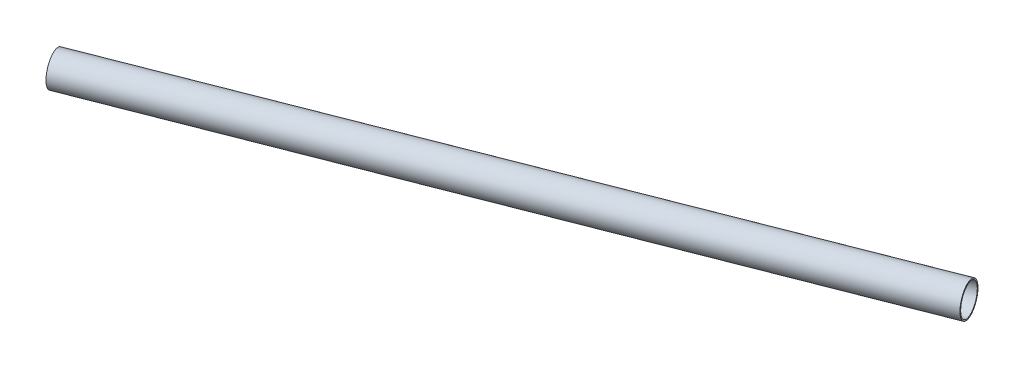
SolidWorks part; units mm, degrees
ref_plane "Front Plane" through (0, 0, 0) normal (0, 0, 1) x (1, 0, 0)
ref_plane "Top Plane" through (0, 0, 0) normal (0, 1, 0) x (1, 0, 0)
ref_plane "Right Plane" through (0, 0, 0) normal (1, 0, 0) x (0, 0, -1)
sketch "Sketch1" plane through (0, 0, 0) normal (0, 1, 0) x (1, 0, 0)
  line L0 (0, 0) -> (640, 0) construction
  line L1 (0, 0) -> (591.2829, 244.9174)
  line L2 (0, 0) -> (591.2829, -244.9174)
  line L3 (0, 0) -> (244.9174, -591.2829)
  line L4 (0, 0) -> (-244.9174, -591.2829)
  line L5 (0, 0) -> (-591.2829, -244.9174)
  line L6 (0, 0) -> (-591.2829, 244.9174)
  line L7 (0, 0) -> (-244.9174, 591.2829)
  line L8 (0, 0) -> (244.9174, 591.2829)
  line L9 (0, 145) -> (55, 145) construction
  line L10 (0, 0) -> (100, 0) construction
  line L11 (0, 0) -> (0, 145) construction
  line L14 (100, 0) -> (100, 145) construction
  circle A0 centre (0, 0) radius 640 construction
  point P15 (0, 0)
  dimension "D1" = 1280
  dimension "D2" = 22.5
  dimension "D4" = 145
  dimension "D5" = 100
  dimension "D6" = 55
  dimension "D3" = 8
sketch "Sketch2" plane through (0, 0, 0) normal (0, 1, 0) x (1, 0, 0)
  line L0 (-486.9956, 169.5033) -> (-66.9956, 169.5033) construction
  line L1 (-188.7141, -86.1278) -> (-188.7141, 241.8722) construction
  line L2 (525.6625, -1048.8053) -> (466.9027, -726.1115) construction
sketch "Sketch3" plane through (0, 0, 0) normal (0, 1, 0) x (1, 0, 0)
  line L0 (0, 0) -> (381.2468, 0) construction
  line L5 (0, 0) -> (0, 199.4415) construction
  line L6 (-10.2736, 158.9263) -> (10.2736, 158.9263)
  line L7 (10.2736, 158.9263) -> (13.1995, 163.9003)
  line L8 (13.1995, 163.9003) -> (45.5131, 148.2994)
  line L9 (45.5131, 148.2994) -> (66.2904, 80.9335)
  line L10 (66.2904, 80.9335) -> (73.8622, 80.9335)
  line L11 (73.8622, 80.9335) -> (86.8684, 42.4396)
  line L12 (86.8684, 42.4396) -> (86.8684, 30.0712)
  line L13 (86.8684, 30.0712) -> (81.3965, 24.5993)
  line L14 (81.3965, 24.5993) -> (81.3965, -24.5993)
  line L15 (-5.8349, 67.4929) -> (5.8349, 67.4929) construction
  line L16 (16.6008, 64.1674) -> (16.6008, 27.6557) construction
  line L17 (16.6008, 27.6557) -> (13.2646, 22.809) construction
  line L18 (13.2646, 22.809) -> (13.2646, -22.809) construction
  line L19 (5.8349, 128.0146) -> (5.8349, 107.4452)
  line L22 (5.8349, 107.4452) -> (9.2702, 107.4452)
  line L25 (9.2702, 107.4452) -> (10.663, 103.7163)
  line L26 (10.663, 103.7163) -> (20.7578, 101.0699)
  line L27 (20.7578, 101.0699) -> (32.199, 111.7601)
  line L28 (32.199, 111.7601) -> (32.199, 123.5038)
  line L29 (32.199, 123.5038) -> (24.9078, 123.5038)
  line L30 (24.9078, 123.5038) -> (13.8412, 132.5856)
  line L31 (13.8412, 132.5856) -> (9.2702, 132.5856)
  line L32 (9.2702, 132.5856) -> (5.8349, 128.0146)
  line L33 (41.9414, 39.7891) -> (51.4866, 54.1602)
  line L34 (51.4866, 54.1602) -> (55.4027, 54.1602)
  line L35 (55.4027, 54.1602) -> (58.1637, 51.3993)
  line L36 (58.1637, 51.3993) -> (58.1637, 43.1872)
  line L37 (58.1637, 43.1872) -> (66.3555, 28.462)
  line L38 (66.3555, 28.462) -> (66.3555, 24.0728)
  line L39 (66.3555, 24.0728) -> (62.2596, 17.9061)
  line L40 (62.2596, 17.9061) -> (47.8497, 18.1669)
  line L41 (47.8497, 18.1669) -> (41.9414, 27.1878)
  line L42 (41.9414, 27.1878) -> (41.9414, 39.7891)
  line L43 (-41.9414, 27.1878) -> (-41.9414, 39.7891)
  line L44 (-47.8497, 18.1669) -> (-41.9414, 27.1878)
  line L45 (-62.2596, 17.9061) -> (-47.8497, 18.1669)
  line L46 (-66.3555, 24.0728) -> (-62.2596, 17.9061)
  line L47 (-66.3555, 28.462) -> (-66.3555, 24.0728)
  line L48 (-58.1637, 43.1872) -> (-66.3555, 28.462)
  line L49 (-58.1637, 51.3993) -> (-58.1637, 43.1872)
  line L50 (-55.4027, 54.1602) -> (-58.1637, 51.3993)
  line L51 (-51.4866, 54.1602) -> (-55.4027, 54.1602)
  line L52 (-41.9414, 39.7891) -> (-51.4866, 54.1602)
  line L53 (-9.2702, 132.5856) -> (-5.8349, 128.0146)
  line L54 (-13.8412, 132.5856) -> (-9.2702, 132.5856)
  line L55 (-24.9078, 123.5038) -> (-13.8412, 132.5856)
  line L56 (-32.199, 123.5038) -> (-24.9078, 123.5038)
  line L57 (-32.199, 111.7601) -> (-32.199, 123.5038)
  line L58 (-20.7578, 101.0699) -> (-32.199, 111.7601)
  line L59 (-10.663, 103.7163) -> (-20.7578, 101.0699)
  line L60 (-9.2702, 107.4452) -> (-10.663, 103.7163)
  line L61 (-5.8349, 107.4452) -> (-9.2702, 107.4452)
  line L62 (-5.8349, 128.0146) -> (-5.8349, 107.4452)
  line L63 (-13.2646, 22.809) -> (-13.2646, -22.809) construction
  line L64 (-16.6008, 27.6557) -> (-13.2646, 22.809) construction
  line L65 (-16.6008, 64.1674) -> (-16.6008, 27.6557) construction
  line L66 (-81.3965, 24.5993) -> (-81.3965, -24.5993)
  line L67 (-86.8684, 30.0712) -> (-81.3965, 24.5993)
  line L68 (-86.8684, 42.4396) -> (-86.8684, 30.0712)
  line L69 (-73.8622, 80.9335) -> (-86.8684, 42.4396)
  line L70 (-66.2904, 80.9335) -> (-73.8622, 80.9335)
  line L71 (-45.5131, 148.2994) -> (-66.2904, 80.9335)
  line L72 (-13.1995, 163.9003) -> (-45.5131, 148.2994)
  line L73 (-10.2736, 158.9263) -> (-13.1995, 163.9003)
  line L74 (-10.2736, -158.9263) -> (-13.1995, -163.9003)
  line L75 (-13.1995, -163.9003) -> (-45.5131, -148.2994)
  line L76 (-45.5131, -148.2994) -> (-66.2904, -80.9335)
  line L77 (-66.2904, -80.9335) -> (-73.8622, -80.9335)
  line L78 (-73.8622, -80.9335) -> (-86.8684, -42.4396)
  line L79 (-86.8684, -42.4396) -> (-86.8684, -30.0712)
  line L80 (-86.8684, -30.0712) -> (-81.3965, -24.5993)
  line L81 (-16.6008, -64.1674) -> (-16.6008, -27.6557) construction
  line L82 (-16.6008, -27.6557) -> (-13.2646, -22.809) construction
  line L83 (-5.8349, -128.0146) -> (-5.8349, -107.4452)
  line L84 (-5.8349, -107.4452) -> (-9.2702, -107.4452)
  line L85 (-9.2702, -107.4452) -> (-10.663, -103.7163)
  line L86 (-10.663, -103.7163) -> (-20.7578, -101.0699)
  line L87 (-20.7578, -101.0699) -> (-32.199, -111.7601)
  line L88 (-32.199, -111.7601) -> (-32.199, -123.5038)
  line L89 (-32.199, -123.5038) -> (-24.9078, -123.5038)
  line L90 (-24.9078, -123.5038) -> (-13.8412, -132.5856)
  line L91 (-13.8412, -132.5856) -> (-9.2702, -132.5856)
  line L92 (-9.2702, -132.5856) -> (-5.8349, -128.0146)
  line L93 (-41.9414, -39.7891) -> (-51.4866, -54.1602)
  line L94 (-51.4866, -54.1602) -> (-55.4027, -54.1602)
  line L95 (-55.4027, -54.1602) -> (-58.1637, -51.3993)
  line L96 (-58.1637, -51.3993) -> (-58.1637, -43.1872)
  line L97 (-58.1637, -43.1872) -> (-66.3555, -28.462)
  line L98 (-66.3555, -28.462) -> (-66.3555, -24.0728)
  line L99 (-66.3555, -24.0728) -> (-62.2596, -17.9061)
  line L100 (-62.2596, -17.9061) -> (-47.8497, -18.1669)
  line L101 (-47.8497, -18.1669) -> (-41.9414, -27.1878)
  line L102 (-41.9414, -27.1878) -> (-41.9414, -39.7891)
  line L103 (41.9414, -27.1878) -> (41.9414, -39.7891)
  line L104 (47.8497, -18.1669) -> (41.9414, -27.1878)
  line L105 (62.2596, -17.9061) -> (47.8497, -18.1669)
  line L106 (66.3555, -24.0728) -> (62.2596, -17.9061)
  line L107 (66.3555, -28.462) -> (66.3555, -24.0728)
  line L108 (58.1637, -43.1872) -> (66.3555, -28.462)
  line L109 (58.1637, -51.3993) -> (58.1637, -43.1872)
  line L110 (55.4027, -54.1602) -> (58.1637, -51.3993)
  line L111 (51.4866, -54.1602) -> (55.4027, -54.1602)
  line L112 (41.9414, -39.7891) -> (51.4866, -54.1602)
  line L113 (9.2702, -132.5856) -> (5.8349, -128.0146)
  line L114 (13.8412, -132.5856) -> (9.2702, -132.5856)
  line L115 (24.9078, -123.5038) -> (13.8412, -132.5856)
  line L116 (32.199, -123.5038) -> (24.9078, -123.5038)
  line L117 (32.199, -111.7601) -> (32.199, -123.5038)
  line L118 (20.7578, -101.0699) -> (32.199, -111.7601)
  line L119 (10.663, -103.7163) -> (20.7578, -101.0699)
  line L120 (9.2702, -107.4452) -> (10.663, -103.7163)
  line L121 (5.8349, -107.4452) -> (9.2702, -107.4452)
  line L122 (5.8349, -128.0146) -> (5.8349, -107.4452)
  line L123 (16.6008, -27.6557) -> (13.2646, -22.809) construction
  line L124 (16.6008, -64.1674) -> (16.6008, -27.6557) construction
  line L125 (-5.8349, -67.4929) -> (5.8349, -67.4929) construction
  line L126 (86.8684, -30.0712) -> (81.3965, -24.5993)
  line L127 (86.8684, -42.4396) -> (86.8684, -30.0712)
  line L128 (73.8622, -80.9335) -> (86.8684, -42.4396)
  line L129 (66.2904, -80.9335) -> (73.8622, -80.9335)
  line L130 (45.5131, -148.2994) -> (66.2904, -80.9335)
  line L131 (13.1995, -163.9003) -> (45.5131, -148.2994)
  line L132 (10.2736, -158.9263) -> (13.1995, -163.9003)
  line L133 (-10.2736, -158.9263) -> (10.2736, -158.9263)
  line L134 (-5.3457, 68.4929) -> (5.3457, 68.4929)
  line L135 (17.6008, 64.1674) -> (17.6008, 27.3448)
  line L136 (17.6008, 27.3448) -> (14.2646, 22.498)
  line L137 (14.2646, 22.498) -> (14.2646, -22.498)
  line L138 (-17.6008, 64.1674) -> (-17.6008, 27.3448)
  line L139 (-17.6008, 27.3448) -> (-14.2646, 22.498)
  line L140 (-5.3457, 68.4929) -> (5.3457, 68.4929) construction
  line L141 (14.2646, 22.498) -> (14.2646, -22.498) construction
  line L142 (17.6008, -27.3448) -> (14.2646, -22.498) construction
  line L143 (17.6008, -64.1674) -> (17.6008, -27.3448) construction
  line L144 (-14.2646, 22.498) -> (-14.2646, -22.498)
  line L145 (17.6008, -64.1674) -> (17.6008, -27.3448)
  line L146 (17.6008, -27.3448) -> (14.2646, -22.498)
  line L147 (-17.6008, -27.3448) -> (-14.2646, -22.498)
  line L148 (-17.6008, -64.1674) -> (-17.6008, -27.3448)
  line L149 (-5.3457, -68.4929) -> (5.3457, -68.4929)
  arc A0 (5.8349, 67.4929) -> (16.6008, 64.0252) centre (10.663, 64.0364) cw construction
  arc A5 (-5.8349, 67.4929) -> (-16.6008, 64.0252) centre (-10.663, 64.0364) ccw construction
  arc A6 (-5.8349, -67.4929) -> (-16.6008, -64.0252) centre (-10.663, -64.0364) cw construction
  arc A7 (5.8349, -67.4929) -> (16.6008, -64.0252) centre (10.663, -64.0364) ccw construction
  arc A8 (-5.3457, 68.4929) -> (-17.6008, 64.0234) centre (-10.663, 64.0364) ccw
  arc A9 (5.3457, 68.4929) -> (17.6008, 64.0234) centre (10.663, 64.0364) cw
  arc A10 (-5.3457, 68.4929) -> (-17.6008, 64.0234) centre (-10.663, 64.0364) ccw construction
  arc A11 (5.3457, -68.4929) -> (17.6008, -64.0234) centre (10.663, -64.0364) ccw
  arc A12 (-5.3457, -68.4929) -> (-17.6008, -64.0234) centre (-10.663, -64.0364) cw
  ellipse E0 centre (11.3851, 149.6854) end of major axis (12.0553, 155.2702) minor radius 3.0047
  ellipse E1 centre (33.6925, 82.363) end of major axis (41.1096, 88.3895) minor radius 4.3287
  ellipse E2 centre (44.8955, 74.0187) end of major axis (51.4866, 79.374) minor radius 4.6847
  ellipse E3 centre (66.3555, 66.447) end of major axis (67.1471, 72.2416) minor radius 3.5711
  ellipse E4 centre (-66.3555, 66.447) end of major axis (-67.1471, 72.2416) minor radius 3.5711
  ellipse E5 centre (-44.8955, 74.0187) end of major axis (-51.4866, 79.374) minor radius 4.6847
  ellipse E6 centre (-33.6925, 82.363) end of major axis (-41.1096, 88.3895) minor radius 4.3287
  ellipse E7 centre (-11.3851, 149.6854) end of major axis (-12.0553, 155.2702) minor radius 3.0047
  ellipse E8 centre (-11.3851, -149.6854) end of major axis (-12.0553, -155.2702) minor radius 3.0047
  ellipse E9 centre (-33.6925, -82.363) end of major axis (-41.1096, -88.3895) minor radius 4.3287
  ellipse E10 centre (-44.8955, -74.0187) end of major axis (-51.4866, -79.374) minor radius 4.6847
  ellipse E11 centre (-66.3555, -66.447) end of major axis (-67.1471, -72.2416) minor radius 3.5711
  ellipse E12 centre (66.3555, -66.447) end of major axis (67.1471, -72.2416) minor radius 3.5711
  ellipse E13 centre (44.8955, -74.0187) end of major axis (51.4866, -79.374) minor radius 4.6847
  ellipse E14 centre (33.6925, -82.363) end of major axis (41.1096, -88.3895) minor radius 4.3287
  ellipse E15 centre (11.3851, -149.6854) end of major axis (12.0553, -155.2702) minor radius 3.0047
  point P117 (0, 67.4929)
  point P126 (0, 158.9263)
  point P180 (0, -158.9263)
  point P181 (0, -67.4929)
  point P190 (-81.3965, 0)
  point P193 (-13.2646, 0)
  point P234 (13.2646, 0)
  point P237 (81.3965, 0)
  point P261 (0, 68.4929)
  point P271 (14.2646, 0)
  point P274 (-14.2646, 0)
  dimension "D1" = 1
sketch "Sketch4" plane through (0, 0, 0) normal (0, 1, 0) x (1, 0, 0)
  line L0 (0, 0) -> (81.2255, 0) construction
  line L1 (0, 0) -> (0, 97.3086) construction
  line L2 (0, 0) -> (0, 199.4415) construction
  line L3 (-10.1399, 86.6928) -> (10.1399, 86.6928)
  line L4 (10.1399, 86.6928) -> (16.0235, 80.8091)
  line L5 (16.0235, 80.8091) -> (23.9736, 57.3032)
  line L6 (23.9736, 57.3032) -> (23.9736, 47.8894)
  line L7 (23.9736, 47.8894) -> (21.6776, 47.8894)
  line L8 (21.6776, 47.8894) -> (21.6776, 27.2256)
  line L9 (21.6776, 27.2256) -> (27.5382, 22.1416)
  line L10 (27.5382, 22.1416) -> (27.5382, 14.9676)
  line L11 (27.5382, 14.9676) -> (23.9736, 10.8585)
  line L12 (23.9736, 10.8585) -> (23.9736, -10.8585)
  line L13 (-23.9736, 10.8585) -> (-23.9736, -10.8585)
  line L14 (-27.5382, 14.9676) -> (-23.9736, 10.8585)
  line L15 (-27.5382, 22.1416) -> (-27.5382, 14.9676)
  line L16 (-21.6776, 27.2256) -> (-27.5382, 22.1416)
  line L17 (-21.6776, 47.8894) -> (-21.6776, 27.2256)
  line L18 (-23.9736, 47.8894) -> (-21.6776, 47.8894)
  line L19 (-23.9736, 57.3032) -> (-23.9736, 47.8894)
  line L20 (-16.0235, 80.8091) -> (-23.9736, 57.3032)
  line L21 (-10.1399, 86.6928) -> (-16.0235, 80.8091)
  line L22 (-10.1399, -86.6928) -> (-16.0235, -80.8091)
  line L23 (-16.0235, -80.8091) -> (-23.9736, -57.3032)
  line L24 (-23.9736, -57.3032) -> (-23.9736, -47.8894)
  line L25 (-23.9736, -47.8894) -> (-21.6776, -47.8894)
  line L26 (-21.6776, -47.8894) -> (-21.6776, -27.2256)
  line L27 (-21.6776, -27.2256) -> (-27.5382, -22.1416)
  line L28 (-27.5382, -22.1416) -> (-27.5382, -14.9676)
  line L29 (-27.5382, -14.9676) -> (-23.9736, -10.8585)
  line L30 (27.5382, -14.9676) -> (23.9736, -10.8585)
  line L31 (27.5382, -22.1416) -> (27.5382, -14.9676)
  line L32 (21.6776, -27.2256) -> (27.5382, -22.1416)
  line L33 (21.6776, -47.8894) -> (21.6776, -27.2256)
  line L34 (23.9736, -47.8894) -> (21.6776, -47.8894)
  line L35 (23.9736, -57.3032) -> (23.9736, -47.8894)
  line L36 (16.0235, -80.8091) -> (23.9736, -57.3032)
  line L37 (10.1399, -86.6928) -> (16.0235, -80.8091)
  line L38 (-10.1399, -86.6928) -> (10.1399, -86.6928)
  point P3 (0, -86.6928)
  point P27 (0, 86.6928)
  point P37 (-23.9736, 0)
  point P38 (23.9736, 0)
sketch "Sketch5" plane through (0, 0, 0) normal (0, 1, 0) x (1, 0, 0)
  line L0 (0, 68.4929) -> (0, 86.6928) construction
  line L1 (15.4511, 110) -> (223.3697, 546.0887)
  line L2 (0, 0) -> (0, 251.8084) construction
  line L3 (0, 110) -> (47.9221, 110) construction
  line L5 (244.9174, 616.9519) -> (262.4572, 609.0616) construction
  line L6 (262.4572, 609.0616) -> (269.1565, 599.6825) construction
  line L7 (269.1565, 599.6825) -> (256.4381, 571.4103) construction
  line L8 (256.4381, 571.4103) -> (244.9174, 563.1812) construction
  line L9 (244.9174, 563.1812) -> (221.08, 517.0826) construction
  line L10 (221.08, 517.0826) -> (201.6817, 527.1134) construction
  line L11 (201.6817, 527.1134) -> (221.6088, 571.4103) construction
  line L12 (221.6088, 571.4103) -> (218.2415, 584.6462) construction
  line L13 (218.2415, 584.6462) -> (232.4366, 616.2011) construction
  line L14 (232.4366, 616.2011) -> (244.9174, 616.9519) construction
  line L15 (244.9174, 591.2829) -> (309.3694, 564.586) construction
  line L16 (269.6266, 526.9284) -> (173.6132, 566.6985) construction
  line L18 (0, 0) -> (107.3069, 0) construction
  dimension "D1" = 110
  dimension "D2" = 50
sketch "Sketch6" plane through (0, 0, 0) normal (0, 1, 0) x (1, 0, 0)
  line L1 (27.9119, 24.7148) -> (544.6401, 226.6863)
  circle A0 centre (0, 0) radius 640 construction
  circle A1 centre (0, 0) radius 640 construction
  circle A3 centre (0, 0) radius 589.9318 construction
  dimension "D1" = 50.0682
sweep "Sweep2" add path "Sketch6" circular profile diameter 25 parameters "D3"=25
sweep "Cut-Sweep2" cut path "Sketch6<2>" circular profile diameter 23 parameters "D3"=23
sketch "Sketch6<2>" plane through (0, 0, 0) normal (0, 1, 0) x (1, 0, 0) same geometry as "Sketch6"
